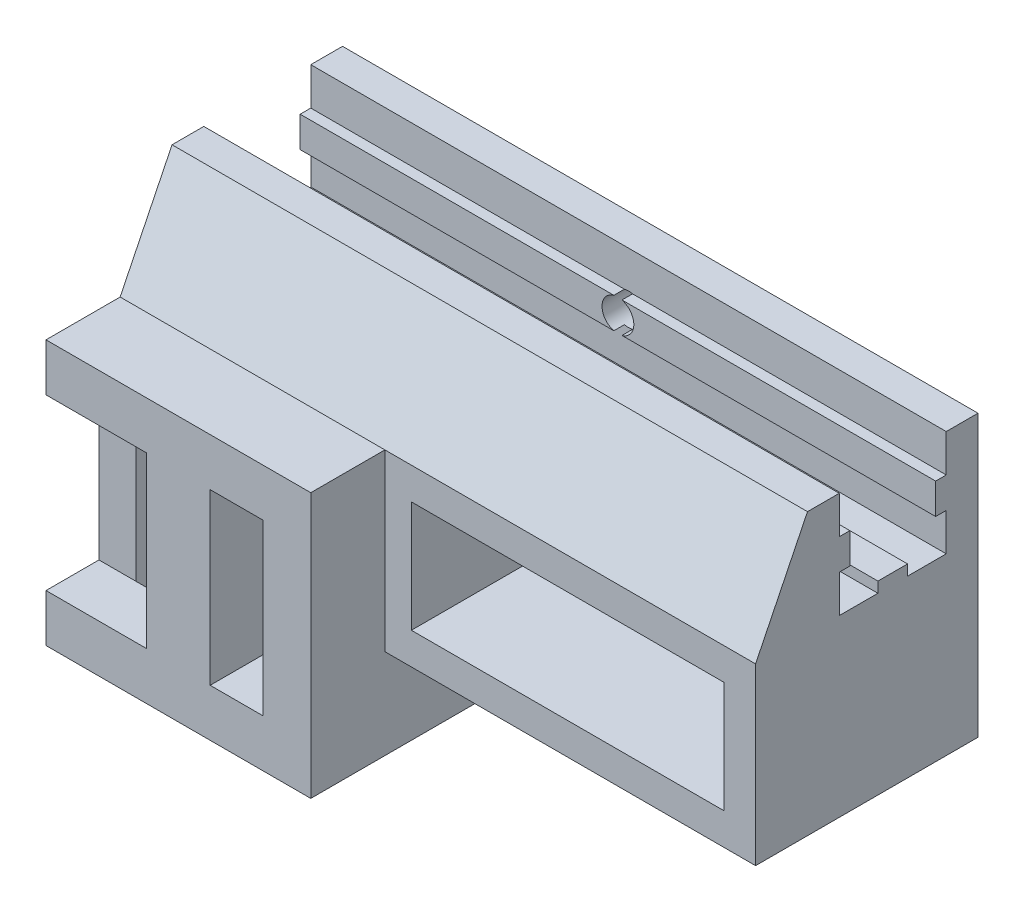
SolidWorks part; units mm, degrees
ref_plane "Front Plane" through (0, 0, 0) normal (0, 0, 1) x (1, 0, 0)
ref_plane "Top Plane" through (0, 0, 0) normal (0, 1, 0) x (1, 0, 0)
ref_plane "Right Plane" through (0, 0, 0) normal (1, 0, 0) x (0, 0, -1)
sketch "Esquisse1" plane through (0, 0, 0) normal (0, 0, 1) x (1, 0, 0)
  line L1 (-30, 17.5) -> (30, 17.5)
  line L2 (-30, 17.5) -> (-30, -17.5)
  line L3 (-30, -17.5) -> (30, -17.5)
  line L4 (30, 17.5) -> (30, -17.5)
  point P4 (-30, 0)
  point P6 (0, 17.5)
  dimension "D1" = 35
  dimension "D2" = 60
extrude "Boss.-Extru.1" add sketch "Esquisse1" along normal blind 3
sketch "Esquisse2" plane through (0, 0, 3) normal (0, 0, 1) x (1, 0, 0)
  line L0 (-30, 17.5) -> (-30, -17.5) construction
  line L1 (-30, 11.05) -> (30, 11.05)
  line L2 (-30, 11.05) -> (-30, 13.95)
  line L3 (-30, 13.95) -> (30, 13.95)
  line L4 (30, 11.05) -> (30, 13.95)
  line L5 (30, -17.5) -> (30, 17.5) construction
  line L6 (30, 17.5) -> (-30, 17.5) construction
  point P8 (-30, 12.5)
  dimension "D1" = 5
  dimension "D2" = 2.9
extrude "Boss.-Extru.2" add sketch "Esquisse2" along normal blind 1
sketch "Esquisse3" plane through (0, 0, 0) normal (0, 0, -1) x (-1, 0, 0)
  line L0 (-30, 11.05) -> (-30, 13.95) construction
  line L1 (-30, 17.5) -> (30, 17.5) construction
  circle A0 centre (0, 12.5) radius 1.5
  point P6 (-30, 12.5)
  point P9 (0, 17.5)
  dimension "D1" = 3
extrude "Enlèv. mat.-Extru.1" cut sketch "Esquisse3" against normal through all
sketch "Esquisse4" plane through (0, 0, 3) normal (0, 0, 1) x (1, 0, 0)
  line L0 (-30, -17.5) -> (30, -17.5) construction
  line L1 (-30, -17.5) -> (-5, -17.5)
  line L2 (-30, -17.5) -> (-30, 7.5)
  line L3 (-30, 7.5) -> (-5, 7.5)
  line L4 (-5, -17.5) -> (-5, 7.5)
  line L5 (-30, 11.05) -> (-30, -17.5) construction
  line L6 (30, 17.5) -> (-30, 17.5) construction
  line L7 (-26.5, 4) -> (-8.5, 4)
  line L8 (-26.5, 4) -> (-26.5, -14)
  line L9 (-26.5, -14) -> (-8.5, -14)
  line L10 (-8.5, 4) -> (-8.5, -14)
  point P6 (-17.5, 4)
  point P13 (-17.5, 7.5)
  point P14 (-26.5, -5)
  point P15 (-30, -5)
  dimension "D1" = 10
  dimension "D2" = 18
  dimension "D3" = 3.5
extrude "Boss.-Extru.3" add sketch "Esquisse4" along normal blind 20
sketch "Esquisse5" plane through (0, 0, 23) normal (0, 0, 1) x (1, 0, 0)
  line L1 (-26.5, 4) -> (-8.5, 4)
  line L2 (-26.5, 4) -> (-26.5, -14)
  line L3 (-26.5, -14) -> (-8.5, -14)
  line L4 (-8.5, 4) -> (-8.5, -14)
extrude "Enlèv. mat.-Extru.2" cut sketch "Esquisse5" against normal through all and the other way through all
sketch "Esquisse6" plane through (0, 0, 23) normal (0, 0, 1) x (1, 0, 0)
  line L0 (-5, 7.5) -> (-30, 7.5) construction
  line L1 (-30, -17.5) -> (-5, -17.5)
  line L2 (-5, -17.5) -> (-5, 7.5)
  line L4 (-30, 7.5) -> (-30, 3)
  line L5 (-30, -17.5) -> (-5, -17.5) construction
  line L6 (-8.5, 4) -> (-26.5, 4) construction
  line L7 (-9.5, 3) -> (-30, 3)
  line L8 (-9.5, 3) -> (-9.5, -13)
  line L9 (-9.5, -13) -> (-30, -13)
  line L12 (-8.5, -14) -> (-8.5, 4) construction
  line L13 (-30, -13) -> (-30, -17.5)
  line L15 (-5, 7.5) -> (-30, 7.5)
  line L16 (-30, 7.5) -> (-30, -17.5) construction
  dimension "D2" = 1
  dimension "D3" = 1
extrude "Boss.-Extru.4" add sketch "Esquisse6" along normal blind 5
sketch "Esquisse7" plane through (0, 0, 28) normal (0, 0, 1) x (1, 0, 0)
  line L0 (-5, 7.5) -> (-30, 7.5) construction
  line L1 (-20.5, 7.5) -> (-14.5, 7.5)
  line L2 (-20.5, 7.5) -> (-20.5, -17.5)
  line L3 (-20.5, -17.5) -> (-14.5, -17.5)
  line L4 (-14.5, 7.5) -> (-14.5, -17.5)
  line L5 (-30, -17.5) -> (-5, -17.5) construction
  line L6 (-26.5, 3) -> (-26.5, -13) construction
  dimension "D1" = 6
  dimension "D2" = 6
extrude "Boss.-Extru.5" add sketch "Esquisse7" against normal up to surface (5 mm away) up to face at (-28.25, -5, 23)
sketch "Esquisse8" plane through (0, 0, 0) normal (0, 0, -1) x (-1, 0, 0)
  line L0 (5, -17.5) -> (5, 7.5) construction
  line L1 (2.5, -6) -> (-27, -6)
  line L2 (2.5, -6) -> (2.5, 4.5)
  line L3 (2.5, 4.5) -> (-27, 4.5)
  line L4 (-27, -6) -> (-27, 4.5)
  line L5 (-30, 17.5) -> (30, 17.5) construction
  dimension "D1" = 10.5
  dimension "D2" = 29.5
  dimension "D3" = 2.5
  dimension "D4" = 13
extrude "Enlèv. mat.-Extru.3" cut sketch "Esquisse8" against normal through all
sketch "Esquisse10" plane through (0, 0, 3) normal (0, 0, 1) x (1, 0, 0)
  line L0 (-5, -17.5) -> (-5, 7.5) construction
  line L1 (-5, -9) -> (30, -9)
  line L2 (-5, -9) -> (-5, 7.5)
  line L3 (-5, 7.5) -> (30, 7.5)
  line L4 (30, -9) -> (30, 7.5)
  line L6 (-2.5, -6) -> (27, -6) construction
  line L7 (27, -6) -> (27, 4.5) construction
  line L8 (30, -17.5) -> (30, 11.05) construction
  line L9 (-2.5, -6) -> (27, -6)
  line L10 (-2.5, -6) -> (-2.5, 4.5)
  line L11 (-2.5, 4.5) -> (27, 4.5)
  line L12 (27, -6) -> (27, 4.5)
  line L13 (-5, 7.5) -> (-30, 7.5) construction
  dimension "D1" = 3
  dimension "D2" = 3
extrude "Boss.-Extru.6" add sketch "Esquisse10" along normal blind 18
sketch "Esquisse11" plane through (0, 0, 3) normal (0, 0, 1) x (1, 0, 0)
  line L1 (-5, -9) -> (30, -9)
  line L2 (-5, -9) -> (-5, -17.5)
  line L3 (-5, -17.5) -> (30, -17.5)
  line L4 (30, -9) -> (30, -17.5)
extrude "Enlèv. mat.-Extru.4" cut sketch "Esquisse11" against normal through all
sketch "Esquisse12" plane through (0, 7.5, 0) normal (0, 1, 0) x (1, 0, 0)
  line L0 (30, -21) -> (30, -3) construction
  line L1 (-30, -9.45) -> (30, -9.45)
  line L2 (-30, -9.45) -> (-30, -6.65)
  line L3 (-30, -6.65) -> (30, -6.65)
  line L4 (30, -9.45) -> (30, -6.65)
  line L5 (-30, -28) -> (-30, -3) construction
  point P9 (-30, -8.05)
  dimension "D1" = 2.8
  dimension "D2" = 5.05
extrude "Boss.-Extru.7" add sketch "Esquisse12" along normal blind 1
sketch "Esquisse13" plane through (30, 0, 0) normal (1, 0, 0) x (0, 0, -1)
  line L0 (-4, 13.95) -> (-3, 13.95) construction
  line L1 (-21, 7.5) -> (-9.45, 7.5) construction
  line L2 (-4, 11.05) -> (-3, 11.05) construction
  line L3 (-13.1, 7.5) -> (-13.1, 11.05)
  line L4 (-13.1, 11.05) -> (-12.1, 11.05)
  line L5 (-12.1, 11.05) -> (-12.1, 13.95)
  line L6 (-12.1, 13.95) -> (-13.1, 13.95)
  line L7 (-13.1, 13.95) -> (-13.1, 17.5)
  line L8 (-13.1, 17.5) -> (-16.1, 17.5)
  line L9 (-16.1, 17.5) -> (-16.1, 7.5)
  line L10 (-16.1, 7.5) -> (-13.1, 7.5)
  line L12 (-3, 7.5) -> (-3, 11.05) construction
  line L13 (-3, 17.5) -> (0, 17.5) construction
  point P5 (-12.6, 13.95)
  dimension "D1" = 10.1
extrude "Boss.-Extru.8" add sketch "Esquisse13" against normal through all
sketch "Esquisse14" plane through (30, 0, 0) normal (1, 0, 0) x (0, 0, -1)
  line L0 (-16.1, 7.5) -> (-16.1, 17.5)
  line L1 (-16.1, 17.5) -> (-16.1, 7.5) construction
  line L2 (-16.1, 17.5) -> (-21, 7.5)
  line L3 (-21, 7.5) -> (-16.1, 7.5)
extrude "Boss.-Extru.9" add sketch "Esquisse14" against normal through all
